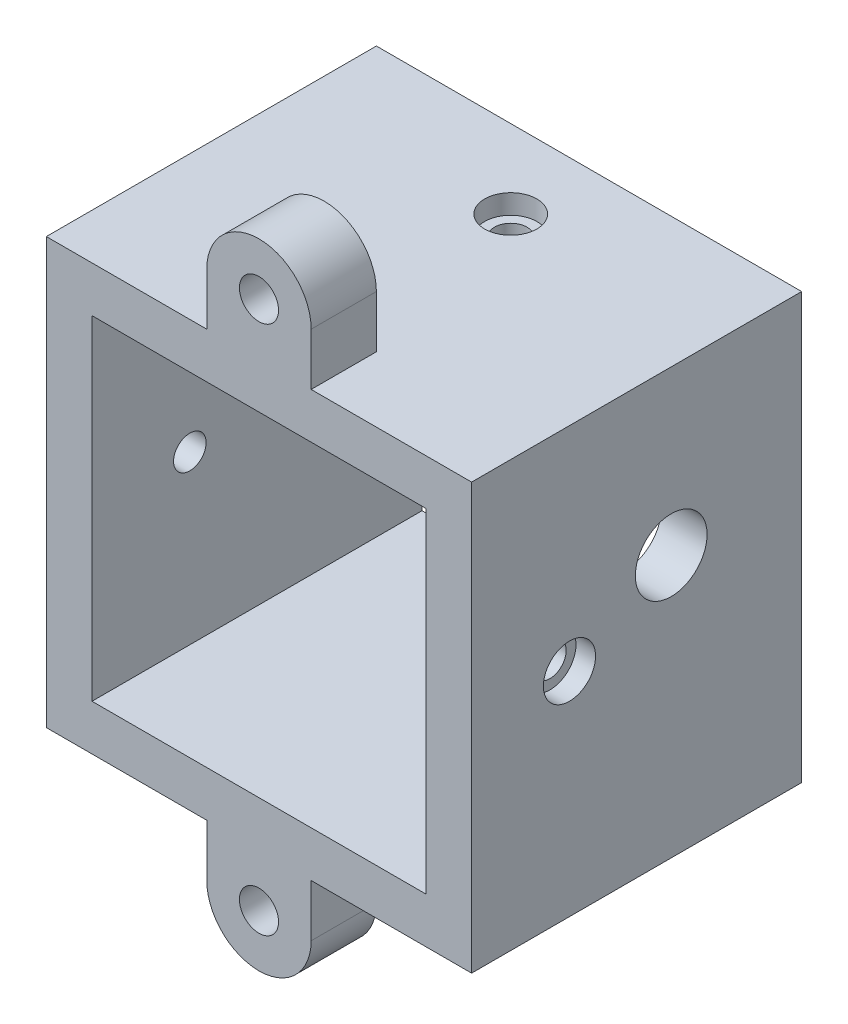
SolidWorks part; units mm, degrees
note: The reader was unsure of these and kept them because the rebuilt part matched: shared geometry of "Esboço1<3>".
ref_plane "Plano frontal" through (0, 0, 0) normal (0, 0, 1) x (1, 0, 0)
ref_plane "Plano superior" through (0, 0, 0) normal (0, 1, 0) x (1, 0, 0)
ref_plane "Plano direito" through (0, 0, 0) normal (1, 0, 0) x (0, 0, -1)
sketch "Esboço1" plane through (0, 0, 0) normal (0, 0, 1) x (1, 0, 0)
  line L0 (-32.6, 32.6) -> (32.6, 32.6)
  line L1 (-25.6, -25.6) -> (25.6, -25.6)
  line L2 (-25.6, -25.6) -> (-25.6, 25.6)
  line L3 (-25.6, 25.6) -> (25.6, 25.6)
  line L4 (25.6, -25.6) -> (25.6, 25.6)
  line L5 (-25.6, -25.6) -> (25.6, 25.6) construction
  line L6 (-25.6, 25.6) -> (25.6, -25.6) construction
  line L7 (32.6, -32.6) -> (32.6, 32.6)
  line L8 (-32.6, -32.6) -> (32.6, -32.6)
  line L9 (-32.6, -32.6) -> (-32.6, 32.6)
  line L10 (-48.087, 0) -> (51.1128, 0) construction
  line L11 (-8, -32.6) -> (8, -32.6)
  line L12 (-8, 32.6) -> (-8, 40.6)
  line L13 (8, -32.6) -> (8, -40.6)
  line L14 (8, 32.6) -> (8, 40.6)
  line L15 (-8, -32.6) -> (-8, -40.6)
  line L16 (8, -32.6) -> (-8, -32.6)
  line L17 (-32.6, -32.6) -> (32.6, -32.6) construction
  line L18 (8, 32.6) -> (-8, 32.6)
  line L19 (-32.6, 32.6) -> (32.6, 32.6) construction
  line L20 (-8, 32.6) -> (8, 32.6)
  arc A0 (8, 40.6) -> (-8, 40.6) centre (0, 40.6) ccw
  circle A1 centre (0, 40.6) radius 3
  arc A2 (8, -40.6) -> (-8, -40.6) centre (0, -40.6) cw
  circle A3 centre (0, -40.6) radius 3
  point P0 (0, 0)
  point P16 (0, 32.6)
  point P17 (0, 32.6)
  dimension "D4" = 8
  dimension "D6" = 6
  dimension "D1" = 51.2
  dimension "D3" = 16
  dimension "D5" = 8
  dimension "D2" = 7
extrude "Ressalto-extrusão1" add sketch "Esboço1" against normal blind 50.6 contours L20 L0 L9 L8 L11 L16 L7 L18 L4 L1 L2 L3 | L1 L4 L3 L2
extrude "Ressalto-extrusão2" add sketch "Esboço1<3>" against normal blind 10 contours L14 A0 L12 L20 A1 | A2 L13 L11 L15 A3
sketch "Esboço1<3>" plane through (0, 0, 0) normal (0, 0, 1) x (1, 0, 0) same geometry as "Esboço1"
sketch "Esboço3" plane through (32.6, 0, 0) normal (1, 0, 0) x (0, 0, -1)
  line L1 (50.6, -32.6) -> (50.6, 32.6) construction
  line L2 (50.6, 32.6) -> (0, 32.6) construction
  circle A0 centre (30.6, 7.6) radius 5.5
  dimension "D1" = 11
  dimension "D2" = 25
  dimension "D3" = 20
extrude "Corte-extrusão2" cut sketch "Esboço3" against normal up to surface (7 mm away) contours A0 up to face at (25.6, 0, -25.3)
sketch "Esboço4" plane through (32.6, 0, 0) normal (1, 0, 0) x (0, 0, -1)
  line L0 (0, -32.6) -> (0, 32.6) construction
  circle A0 centre (15, 0) radius 2.5
  dimension "D2" = 5
  dimension "D1" = 15
extrude "Corte-extrusão3" cut sketch "Esboço4" against normal through all
sketch "Esboço5" plane through (32.6, 0, 0) normal (1, 0, 0) x (0, 0, -1)
  circle A0 centre (15, 0) radius 4
  dimension "D1" = 8
extrude "Corte-extrusão4" cut sketch "Esboço5" against normal blind 3
mirror "Espelhar1" about plane through (0, 0, 0) normal (1, 0, 0) of "Corte-extrusão4"
sketch "Esboço6" plane through (0, 32.6, 0) normal (0, 1, 0) x (1, 0, 0)
  line L0 (-32.6, 50.6) -> (32.6, 50.6) construction
  circle A0 centre (0, 38.6) radius 2.5
  dimension "D1" = 5
  dimension "D2" = 12
extrude "Corte-extrusão5" cut sketch "Esboço6" against normal up to surface (7 mm away) up to face at (0, 25.6, -25.3)
sketch "Esboço7" plane through (0, 32.6, 0) normal (0, 1, 0) x (1, 0, 0)
  circle A0 centre (0, 38.6) radius 4
  dimension "D1" = 8
extrude "Corte-extrusão6" cut sketch "Esboço7" against normal blind 3
